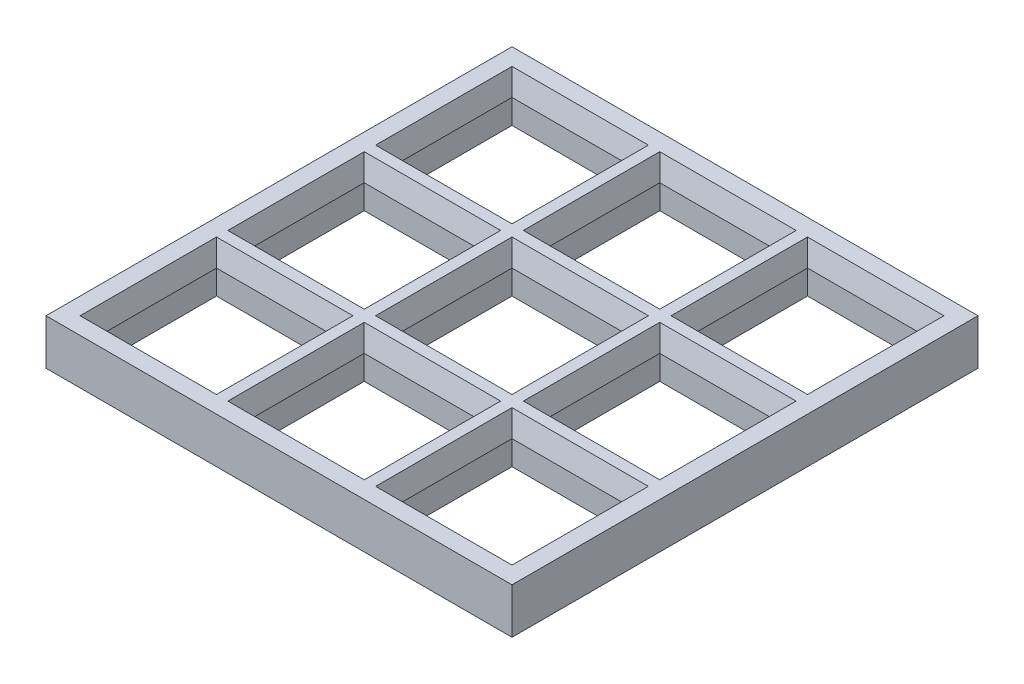
SolidWorks part; units mm, degrees
ref_plane "Front Plane" through (0, 0, 0) normal (0, 0, 1) x (1, 0, 0)
ref_plane "Top Plane" through (0, 0, 0) normal (0, 1, 0) x (1, 0, 0)
ref_plane "Right Plane" through (0, 0, 0) normal (1, 0, 0) x (0, 0, -1)
sketch "Sketch2" plane through (0, 0, 0) normal (0, 1, 0) x (1, 0, 0)
  line L1 (102.5, -102.5) -> (-102.5, -102.5)
  line L2 (102.5, -102.5) -> (102.5, 102.5)
  line L3 (102.5, 102.5) -> (-102.5, 102.5)
  line L4 (-102.5, -102.5) -> (-102.5, 102.5)
  line L5 (102.5, -102.5) -> (-102.5, 102.5) construction
  line L6 (102.5, 102.5) -> (-102.5, -102.5) construction
  point P0 (0, 0)
  dimension "D1" = 205
  dimension "D2" = 205
extrude "Boss-Extrude1" add sketch "Sketch2" along normal blind 20
sketch "Sketch3" plane through (0, 20, 0) normal (0, 1, 0) x (1, 0, 0)
  line L0 (-102.5, 102.5) -> (-102.5, -102.5) construction
  line L1 (-92.5, 37.5) -> (-37.5, 37.5)
  line L2 (-92.5, 37.5) -> (-92.5, 92.5)
  line L3 (-92.5, 92.5) -> (-37.5, 92.5)
  line L4 (-37.5, 37.5) -> (-37.5, 92.5)
  line L5 (-92.5, 37.5) -> (-37.5, 92.5) construction
  line L6 (-92.5, 92.5) -> (-37.5, 37.5) construction
  line L7 (102.5, 102.5) -> (-102.5, 102.5) construction
  point P0 (-65, 65)
  dimension "D1" = 55
  dimension "D2" = 55
  dimension "D3" = 10
  dimension "D4" = 10
extrude "Cut-Extrude1" cut sketch "Sketch3" against normal through all
pattern_linear "LPattern1" count 3 spacing 65 along (1, 0, 0) count 3 spacing 65 along (0, 0, 1) of "Cut-Extrude1"
chamfer "Chamfer1" distance 2.5 angle 75 36 edges at (65, 20, 37.5) (37.5, 20, 65) (65, 20, 92.5) (92.5, 20, 65) (0, 20, 37.5) (-27.5, 20, 65) (0, 20, 92.5) (27.5, 20, 65) (-65, 20, 37.5) (-92.5, 20, 65) (-65, 20, 92.5) (-37.5, 20, 65) (65, 20, -27.5) (37.5, 20, 0) (65, 20, 27.5) (92.5, 20, 0) (0, 20, -27.5) (-27.5, 20, 0) (0, 20, 27.5) (27.5, 20, 0) (65, 20, -92.5) (37.5, 20, -65) (65, 20, -37.5) (92.5, 20, -65) (-65, 20, -92.5) (-92.5, 20, -65) (-65, 20, -37.5) (-37.5, 20, -65) (0, 20, -92.5) (-27.5, 20, -65) (0, 20, -37.5) (27.5, 20, -65) (-92.5, 20, 0) (-65, 20, 27.5) (-37.5, 20, 0) (-65, 20, -27.5) first distance on face at (0, 20, -65)
